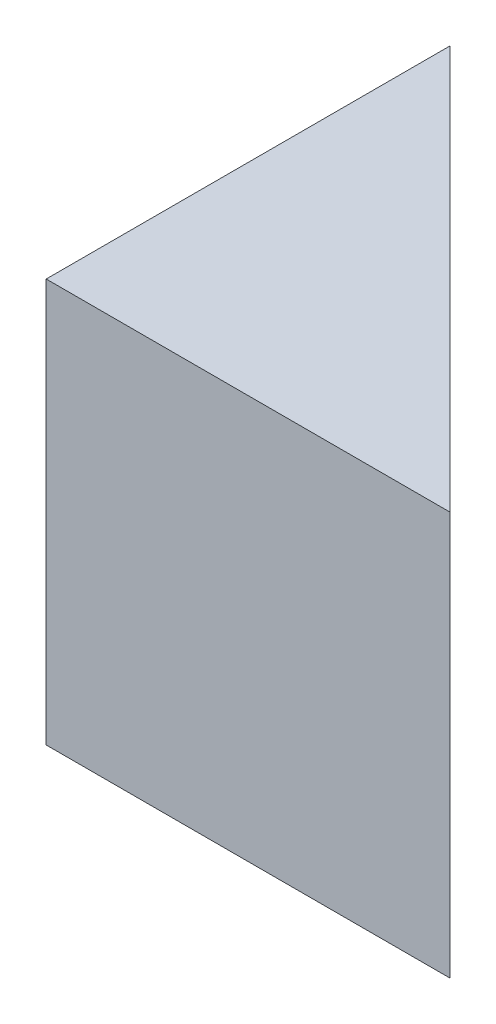
SolidWorks part; units mm, degrees
ref_plane "Front Plane" through (0, 0, 0) normal (0, 0, 1) x (1, 0, 0)
ref_plane "Top Plane" through (0, 0, 0) normal (0, 1, 0) x (1, 0, 0)
ref_plane "Right Plane" through (0, 0, 0) normal (1, 0, 0) x (0, 0, -1)
sketch "Sketch1" plane through (0, 0, 0) normal (0, 1, 0) x (1, 0, 0)
  line L0 (0, 0) -> (0, 30)
  line L1 (0, 30) -> (30, 0)
  line L2 (30, 0) -> (0, 0)
  dimension "D1" = 30
extrude "Boss-Extrude1" add sketch "Sketch1" along normal blind 30
